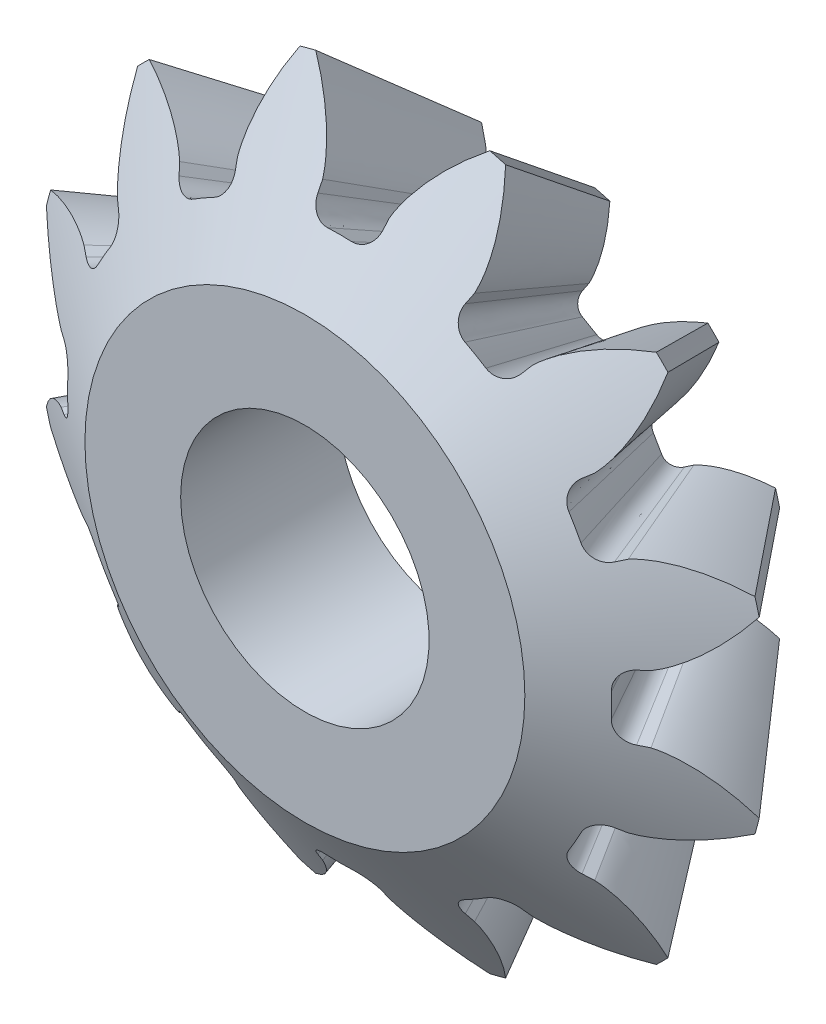
SolidWorks part; units mm, degrees
ref_plane "Front Plane" through (0, 0, 0) normal (0, 0, 1) x (1, 0, 0)
ref_plane "Top Plane" through (0, 0, 0) normal (0, 1, 0) x (1, 0, 0)
ref_plane "Right Plane" through (0, 0, 0) normal (1, 0, 0) x (0, 0, -1)
ref_axis "Gear Axis" through (0, 0, -0.9465) along (0, 0, 1)
sketch "Blank Sketch" plane through (0, 0, 0) normal (0, 1, 0) x (1, 0, 0)
  line L0 (0, 0) -> (0, -18.9291) construction
  line L1 (0, 0) -> (10.5, -15.75) construction
  line L2 (0, 0) -> (7.1718, -10.7577) construction
  line L3 (4.4944, -12.5426) -> (8.3337, -9.9831)
  line L4 (8.3337, -9.9831) -> (12.3282, -14.5312)
  line L5 (12.3282, -14.5312) -> (7.3923, -17.8218)
  line L6 (7.3923, -17.8218) -> (4.175, -17.8218)
  line L7 (4.175, -17.8218) -> (4.175, -12.5426)
  line L8 (4.175, -12.5426) -> (4.4944, -12.5426)
  line L9 (10.5, -15.75) -> (12.3282, -14.5312) construction
  line L10 (10.5, -15.75) -> (7.3923, -17.8218) construction
  line L11 (7.1718, -10.7577) -> (4.4944, -12.5426) construction
  dimension "Axis" = 18.9291
  dimension "Cone" = 33.69
  dimension "Heel" = 18.9291
  dimension "Toe Cone" = 33.69
  dimension "Toe" = 12.9291
  dimension "Heel Square" = 90
  dimension "Addendum" = 2.1972
  dimension "Root Square" = 90
  dimension "Heel Rim" = 3.735
  dimension "Toe Square" = 90
  dimension "Toe Rim" = 3.2178
  dimension "Front Square" = 90
  dimension "Face" = 7.602
  dimension "Back" = 3.2173
  dimension "Front" = 0.3194
revolve "Blank" add sketch "Blank Sketch" angle 360 about L0
sketch "Cone Sketch" plane through (0, 0, 0) normal (0, 1, 0) x (1, 0, 0)
  line L0 (0, 0) -> (0, -18.9291) construction
  line L1 (0, 0) -> (11.4707, -17.2061)
  line L2 (0, 0) -> (6.2011, -9.3016)
  dimension "Axis" = 18.9291
  dimension "Toe Cone" = 33.69
  dimension "Heel Cone" = 33.69
  dimension "Heel" = 20.6791
  dimension "Toe" = 11.1791
ref_plane "Heel Plane" through (11.4707, 0, 17.2061) normal (0.5547, 0, 0.8321) x (0.8321, 0, -0.5547)
ref_plane "Toe Plane" through (6.2011, 0, 9.3016) normal (0.5547, 0, 0.8321) x (0.8321, 0, -0.5547)
sketch "Heel Section Sketch" plane through (11.4707, 0, 17.2061) normal (0.5547, 0, 0.8321) x (0.8321, 0, -0.5547)
  line L0 (0, 0) -> (-13.7861, 0) construction
  line L1 (-0.7508, 1.2294) -> (-1.1331, 1.1934)
  line L2 (-0.7508, -1.2294) -> (-1.1331, -1.1934)
  line L3 (3.5275, 5.2711) -> (3.5275, -5.2711)
  arc A0 (-1.1331, 1.1934) -> (-1.7908, 0.4433) centre (-1.0648, 0.4701) ccw
  arc A1 (-1.7908, -0.4433) -> (-1.1331, -1.1934) centre (-1.0648, -0.4701) ccw
  arc A2 (-1.7908, -0.4433) -> (-1.7908, 0.4433) centre (-13.7861, 0) ccw
  spline S0 degree 4 poles (-0.8643, 1.2058) (-0.8309, 1.2118) (-0.7731, 1.2233) (-0.7135, 1.2381) (-0.5804, 1.2766) (-0.4653, 1.3174) (-0.312, 1.3766) (-0.1596, 1.4452) (0.011, 1.5288) (0.1737, 1.6174) (0.3361, 1.7124) (0.4936, 1.8119) (0.6625, 1.9255) (0.865, 2.071) (1.0994, 2.254) (1.3602, 2.4755) (1.6347, 2.7324) (1.8957, 2.9964) (2.1495, 3.2774) (2.3866, 3.557) (2.6229, 3.8626) (2.833, 4.1472) (3.059, 4.4866) (3.2317, 4.7538) (3.4548, 5.1378) (3.5715, 5.3491) (3.7117, 5.6164) (3.7705, 5.7356) (3.8051, 5.8059) knots 0 0 0 0 0 0.016753 0.031571 0.050064 0.068907 0.096646 0.124386 0.152126 0.179865 0.207605 0.235344 0.263084 0.300343 0.355823 0.411302 0.466781 0.52226 0.577739 0.633218 0.688697 0.744176 0.799656 0.855135 0.910614 0.955307 1 1 1 1 1 construction
  spline S1 degree 4 poles (-0.7508, 1.2294) (-0.7291, 1.2347) (-0.6812, 1.2475) (-0.5804, 1.2766) (-0.4653, 1.3174) (-0.312, 1.3766) (-0.1596, 1.4452) (0.011, 1.5288) (0.1737, 1.6174) (0.3361, 1.7124) (0.4936, 1.8119) (0.6625, 1.9255) (0.865, 2.071) (1.0994, 2.254) (1.3602, 2.4755) (1.6347, 2.7324) (1.8957, 2.9964) (2.1495, 3.2774) (2.3866, 3.557) (2.6229, 3.8626) (2.833, 4.1472) (3.059, 4.4866) (3.2317, 4.7538) (3.4076, 5.0565) (3.4873, 5.1978) (3.5275, 5.2711) knots 0.016753 0.016753 0.016753 0.016753 0.016753 0.031571 0.050064 0.068907 0.096646 0.124386 0.152126 0.179865 0.207605 0.235344 0.263084 0.300343 0.355823 0.411302 0.466781 0.52226 0.577739 0.633218 0.688697 0.744176 0.799656 0.855135 0.910614 0.910614 0.910614 0.910614 0.910614
  spline S2 degree 4 poles (-0.8643, -1.2058) (-0.8309, -1.2118) (-0.7731, -1.2233) (-0.7135, -1.2381) (-0.5804, -1.2766) (-0.4653, -1.3174) (-0.312, -1.3766) (-0.1596, -1.4452) (0.011, -1.5288) (0.1737, -1.6174) (0.3361, -1.7124) (0.4936, -1.8119) (0.6625, -1.9255) (0.865, -2.071) (1.0994, -2.254) (1.3602, -2.4755) (1.6347, -2.7324) (1.8957, -2.9964) (2.1495, -3.2774) (2.3866, -3.557) (2.6229, -3.8626) (2.833, -4.1472) (3.059, -4.4866) (3.2317, -4.7538) (3.4548, -5.1378) (3.5715, -5.3491) (3.7117, -5.6164) (3.7705, -5.7356) (3.8051, -5.8059) knots 0 0 0 0 0 0.016753 0.031571 0.050064 0.068907 0.096646 0.124386 0.152126 0.179865 0.207605 0.235344 0.263084 0.300343 0.355823 0.411302 0.466781 0.52226 0.577739 0.633218 0.688697 0.744176 0.799656 0.855135 0.910614 0.955307 1 1 1 1 1 construction
  spline S3 degree 4 poles (-0.7508, -1.2294) (-0.7291, -1.2347) (-0.6812, -1.2475) (-0.5804, -1.2766) (-0.4653, -1.3174) (-0.312, -1.3766) (-0.1596, -1.4452) (0.011, -1.5288) (0.1737, -1.6174) (0.3361, -1.7124) (0.4936, -1.8119) (0.6625, -1.9255) (0.865, -2.071) (1.0994, -2.254) (1.3602, -2.4755) (1.6347, -2.7324) (1.8957, -2.9964) (2.1495, -3.2774) (2.3866, -3.557) (2.6229, -3.8626) (2.833, -4.1472) (3.059, -4.4866) (3.2317, -4.7538) (3.4076, -5.0565) (3.4873, -5.1978) (3.5275, -5.2711) knots 0.016753 0.016753 0.016753 0.016753 0.016753 0.031571 0.050064 0.068907 0.096646 0.124386 0.152126 0.179865 0.207605 0.235344 0.263084 0.300343 0.355823 0.411302 0.466781 0.52226 0.577739 0.633218 0.688697 0.744176 0.799656 0.855135 0.910614 0.910614 0.910614 0.910614 0.910614
  dimension "Root" = 12.0035
  dimension "Fillet" = 0.7265
  dimension "Centre" = 13.7861
sketch "Toe Section Sketch" plane through (6.2011, 0, 9.3016) normal (0.5547, 0, 0.8321) x (0.8321, 0, -0.5547)
  line L0 (0, 0) -> (-7.4528, 0) construction
  line L1 (-0.4059, 0.6646) -> (-0.6125, 0.6451)
  line L2 (-0.4059, -0.6646) -> (-0.6125, -0.6451)
  line L3 (1.907, 2.8496) -> (1.907, -2.8496)
  arc A0 (-0.6125, 0.6451) -> (-0.9681, 0.2396) centre (-0.5757, 0.2541) ccw
  arc A1 (-0.9681, -0.2396) -> (-0.6125, -0.6451) centre (-0.5757, -0.2541) ccw
  arc A2 (-0.9681, -0.2396) -> (-0.9681, 0.2396) centre (-7.4528, 0) ccw
  spline S0 degree 4 poles (-0.4672, 0.6518) (-0.4492, 0.6551) (-0.418, 0.6613) (-0.3857, 0.6693) (-0.3138, 0.6901) (-0.2516, 0.7122) (-0.1687, 0.7442) (-0.0863, 0.7813) (0.0059, 0.8265) (0.0939, 0.8744) (0.1817, 0.9257) (0.2669, 0.9795) (0.3582, 1.0409) (0.4676, 1.1196) (0.5944, 1.2185) (0.7353, 1.3383) (0.8837, 1.4771) (1.0248, 1.6199) (1.162, 1.7718) (1.2902, 1.9229) (1.418, 2.0881) (1.5315, 2.242) (1.6537, 2.4254) (1.7471, 2.5699) (1.8676, 2.7775) (1.9308, 2.8917) (2.0066, 3.0362) (2.0383, 3.1006) (2.0571, 3.1387) knots 0 0 0 0 0 0.016753 0.031571 0.050064 0.068907 0.096646 0.124386 0.152126 0.179865 0.207605 0.235344 0.263084 0.300343 0.355823 0.411302 0.466781 0.52226 0.577739 0.633218 0.688697 0.744176 0.799656 0.855135 0.910614 0.955307 1 1 1 1 1 construction
  spline S1 degree 4 poles (-0.4059, 0.6646) (-0.3941, 0.6675) (-0.3682, 0.6744) (-0.3138, 0.6901) (-0.2516, 0.7122) (-0.1687, 0.7442) (-0.0863, 0.7813) (0.0059, 0.8265) (0.0939, 0.8744) (0.1817, 0.9257) (0.2669, 0.9795) (0.3582, 1.0409) (0.4676, 1.1196) (0.5944, 1.2185) (0.7353, 1.3383) (0.8837, 1.4771) (1.0248, 1.6199) (1.162, 1.7718) (1.2902, 1.9229) (1.418, 2.0881) (1.5315, 2.242) (1.6537, 2.4254) (1.7471, 2.5699) (1.8421, 2.7335) (1.8852, 2.81) (1.907, 2.8496) knots 0.016753 0.016753 0.016753 0.016753 0.016753 0.031571 0.050064 0.068907 0.096646 0.124386 0.152126 0.179865 0.207605 0.235344 0.263084 0.300343 0.355823 0.411302 0.466781 0.52226 0.577739 0.633218 0.688697 0.744176 0.799656 0.855135 0.910614 0.910614 0.910614 0.910614 0.910614
  spline S2 degree 4 poles (-0.4672, -0.6518) (-0.4492, -0.6551) (-0.418, -0.6613) (-0.3857, -0.6693) (-0.3138, -0.6901) (-0.2516, -0.7122) (-0.1687, -0.7442) (-0.0863, -0.7813) (0.0059, -0.8265) (0.0939, -0.8744) (0.1817, -0.9257) (0.2669, -0.9795) (0.3582, -1.0409) (0.4676, -1.1196) (0.5944, -1.2185) (0.7353, -1.3383) (0.8837, -1.4771) (1.0248, -1.6199) (1.162, -1.7718) (1.2902, -1.9229) (1.418, -2.0881) (1.5315, -2.242) (1.6537, -2.4254) (1.7471, -2.5699) (1.8676, -2.7775) (1.9308, -2.8917) (2.0066, -3.0362) (2.0383, -3.1006) (2.0571, -3.1387) knots 0 0 0 0 0 0.016753 0.031571 0.050064 0.068907 0.096646 0.124386 0.152126 0.179865 0.207605 0.235344 0.263084 0.300343 0.355823 0.411302 0.466781 0.52226 0.577739 0.633218 0.688697 0.744176 0.799656 0.855135 0.910614 0.955307 1 1 1 1 1 construction
  spline S3 degree 4 poles (-0.4059, -0.6646) (-0.3941, -0.6675) (-0.3682, -0.6744) (-0.3138, -0.6901) (-0.2516, -0.7122) (-0.1687, -0.7442) (-0.0863, -0.7813) (0.0059, -0.8265) (0.0939, -0.8744) (0.1817, -0.9257) (0.2669, -0.9795) (0.3582, -1.0409) (0.4676, -1.1196) (0.5944, -1.2185) (0.7353, -1.3383) (0.8837, -1.4771) (1.0248, -1.6199) (1.162, -1.7718) (1.2902, -1.9229) (1.418, -2.0881) (1.5315, -2.242) (1.6537, -2.4254) (1.7471, -2.5699) (1.8421, -2.7335) (1.8852, -2.81) (1.907, -2.8496) knots 0.016753 0.016753 0.016753 0.016753 0.016753 0.031571 0.050064 0.068907 0.096646 0.124386 0.152126 0.179865 0.207605 0.235344 0.263084 0.300343 0.355823 0.411302 0.466781 0.52226 0.577739 0.633218 0.688697 0.744176 0.799656 0.855135 0.910614 0.910614 0.910614 0.910614 0.910614
  dimension "Root" = 6.4891
  dimension "Fillet" = 0.3927
  dimension "Centre" = 7.4528
loft "Tooth Space" cut profiles "Heel Section Sketch", "Toe Section Sketch"
pattern_circular "Teeth" count 12 over 360 about axis through (0, 0, -0.9465) along (0, 0, 1) of "Tooth Space"
equation "\"No. of Teeth\"= 12"
equation "\"Module\"= 1.75"
equation "\"Bore Diameter\"= 8.35"
equation "\"Pressure Angle\"= 20"
equation "\"Shaft Angle\"= 90"
equation "\"Mate Teeth\"= 18"
equation "\"Pitch Cone Angle\"= IIF ( ( \"Mate Teeth\" / \"No. of Teeth\" + cos ( \"Shaft Angle\" ) ) > 0 , atn ( sin ( \"Shaft Angle\" ) / ( \"Mate Teeth\" / \"No. of Teeth\" + cos ( \"Shaft Angle\" ) ) ) , 180 + atn ( sin ( \"Shaft Angle\" ) / ( \"Mate Teeth\" / \"No. of Teeth\" + cos ( \"Shaft Angle\" ) ) ) )"
equation "\"Mate Cone Angle\"= \"Shaft Angle\" - \"Pitch Cone Angle\""
equation "\"Addendum\"= IIF ( \"No. of Teeth\" >= \"Mate Teeth\" , 0.54 * \"Module\" + 0.46 * \"Module\" / ( ( \"No. of Teeth\" * cos ( \"Mate Cone Angle\" ) ) / ( \"Mate Teeth\" * cos ( \"Pitch Cone Angle\" ) ) ) , 2 * \"Module\" - ( 0.54 * \"Module\" + 0.46 * \"Module\" / ( ( \"Mate Teeth\" * cos ( \"Pitch Cone Angle\" ) ) / ( \"No. of Teeth\" * cos ( \"Mate Cone Angle\" ) ) ) ) )"
equation "\"Outer Diameter\"= \"No. of Teeth\" * \"Module\" + 2 * \"Addendum\" * cos ( \"Pitch Cone Angle\" )"
equation "\"Pitch Diameter\"= \"No. of Teeth\" * \"Module\""
equation "\"Backlash\"= IIF ( \"Module\" <= 1 , 0.3 * \"Module\" , 0.3 )"
equation "\"Arc Length\"= ( ( \"Module\" * pi ) / 2 + \"Backlash\" - 2 * ( \"Addendum\" - \"Module\" ) * tan ( \"Pressure Angle\" ) )"
equation "\"Fillet Radius\"= 0.38 * \"Module\""
equation "\"Mate Addendum\"= 2 * \"Module\" - \"Addendum\""
equation "\"Dedendum\"= 2.188 * \"Module\" - \"Addendum\""
equation "\"Tooth Depth\"= \"Addendum\" + \"Dedendum\""
equation "\"Mate Dedendum\"= 2.188 * \"Module\" - \"Mate Addendum\""
equation "\"Face Width\"= 6"
equation "\"Cone Distance\"= \"Pitch Diameter\" / ( 2 * sin ( \"Pitch Cone Angle\" ) )"
equation "\"Dedendum Angle\"= atn ( \"Dedendum\" / \"Cone Distance\" )"
equation "\"Mate Dedendum Angle\"= atn ( \"Mate Dedendum\" / \"Cone Distance\" )"
equation "\"Face Angle\"= \"Pitch Cone Angle\" + \"Mate Dedendum Angle\""
equation "\"Root Angle\"= \"Pitch Cone Angle\" - \"Dedendum Angle\""
equation "\"Overrun\"= \"Module\""
equation "\"Back Cone Pitch Diameter\"= \"Pitch Diameter\" / cos ( \"Pitch Cone Angle\" )"
equation "\"Back Cone Outer Diameter\"= \"Back Cone Pitch Diameter\" + 2 * \"Addendum\""
equation "\"Root Diameter\"= \"Back Cone Outer Diameter\" - 2 * \"Tooth Depth\""
equation "\"Base Diameter\"= \"Back Cone Pitch Diameter\" * cos ( \"Pressure Angle\" )"
equation "\"Base Radius\"= \"Base Diameter\" / 2"
equation "\"Tooth Thickness\"= \"Module\" * pi - \"Arc Length\""
equation "\"Half Space Angle\"= ( \"Arc Length\" / \"Back Cone Pitch Diameter\" ) * 180 / pi"
equation "\"Involute Fn\"= tan ( \"Pressure Angle\" ) - \"Pressure Angle\" * pi / 180"
equation "\"Flank Offset\"= \"Arc Length\" / \"Back Cone Pitch Diameter\" - \"Involute Fn\""
equation "\"Tip Cap Diameter\"= \"Back Cone Outer Diameter\" + 2 * \"Module\""
equation "\"Flank Start Diameter\"= IIF ( \"Base Diameter\" >= ( \"Root Diameter\" + 3 * \"Fillet Radius\" ) , \"Base Diameter\" , \"Root Diameter\" + 3 * \"Fillet Radius\" )"
equation "\"Involute t1\"= ( abs ( ( \"Flank Start Diameter\" / \"Base Diameter\" ) ^ 2 - 1 ) ) ^ 0.5"
equation "\"Involute t2\"= ( abs ( ( \"Tip Cap Diameter\" / \"Base Diameter\" ) ^ 2 - 1 ) ) ^ 0.5"
equation "\"Flank Arc Radius\"= ( \"Back Cone Pitch Diameter\" / 2 ) * sin ( \"Pressure Angle\" )"
equation "\"Flank Centre Angle\"= \"Half Space Angle\" + \"Pressure Angle\""
equation "\"Heel Distance\"= \"Cone Distance\" + \"Overrun\""
equation "\"Toe Distance\"= \"Cone Distance\" - \"Face Width\" - \"Overrun\""
equation "\"Heel Scale\"= \"Heel Distance\" / \"Cone Distance\""
equation "\"Toe Scale\"= \"Toe Distance\" / \"Cone Distance\""
equation "\"Heel Virtual Radius\"= \"Heel Distance\" * tan ( \"Pitch Cone Angle\" )"
equation "\"Toe Virtual Radius\"= \"Toe Distance\" * tan ( \"Pitch Cone Angle\" )"
equation "\"Axis@Blank Sketch\"= \"Cone Distance\""
equation "\"Cone@Blank Sketch\"= \"Pitch Cone Angle\""
equation "\"Heel@Blank Sketch\"= \"Cone Distance\""
equation "\"Toe Cone@Blank Sketch\"= \"Pitch Cone Angle\""
equation "\"Toe@Blank Sketch\"= \"Cone Distance\" - \"Face Width\""
equation "\"Addendum@Blank Sketch\"= \"Addendum\""
equation "\"Heel Rim@Blank Sketch\"= \"Dedendum\" + \"Module\" / cos ( \"Pitch Cone Angle\" )"
equation "\"Toe Rim@Blank Sketch\"= \"Dedendum\" - \"Face Width\" * tan ( \"Dedendum Angle\" ) + \"Module\" / cos ( \"Pitch Cone Angle\" )"
equation "\"Face@Blank Sketch\"= \"Mate Dedendum Angle\""
equation "\"Back@Blank Sketch\"= \"Cone Distance\" * sin ( \"Pitch Cone Angle\" ) - \"Dedendum\" * cos ( \"Pitch Cone Angle\" ) - \"Module\" - \"Bore Diameter\" / 2"
equation "\"Front@Blank Sketch\"= ( \"Cone Distance\" - \"Face Width\" ) * sin ( \"Pitch Cone Angle\" ) - ( \"Dedendum\" - \"Face Width\" * tan ( \"Dedendum Angle\" ) + \"Module\" / cos ( \"Pitch Cone Angle\" ) ) * cos ( \"Pitch Cone Angle\" ) - \"Bore Diameter\" / 2"
equation "\"Axis@Cone Sketch\"= \"Cone Distance\""
equation "\"Heel Cone@Cone Sketch\"= \"Pitch Cone Angle\""
equation "\"Heel@Cone Sketch\"= \"Heel Distance\""
equation "\"Toe Cone@Cone Sketch\"= \"Pitch Cone Angle\""
equation "\"Toe@Cone Sketch\"= \"Toe Distance\""
equation "\"Centre@Heel Section Sketch\"= \"Heel Virtual Radius\""
equation "\"Root@Heel Section Sketch\"= ( \"Root Diameter\" / 2 ) * \"Heel Scale\""
equation "\"Fillet@Heel Section Sketch\"= ( \"Fillet Radius\" ) * \"Heel Scale\""
equation "\"Centre@Toe Section Sketch\"= \"Toe Virtual Radius\""
equation "\"Root@Toe Section Sketch\"= ( \"Root Diameter\" / 2 ) * \"Toe Scale\""
equation "\"Fillet@Toe Section Sketch\"= ( \"Fillet Radius\" ) * \"Toe Scale\""
equation "\"Count@Teeth\"= \"No. of Teeth\""
